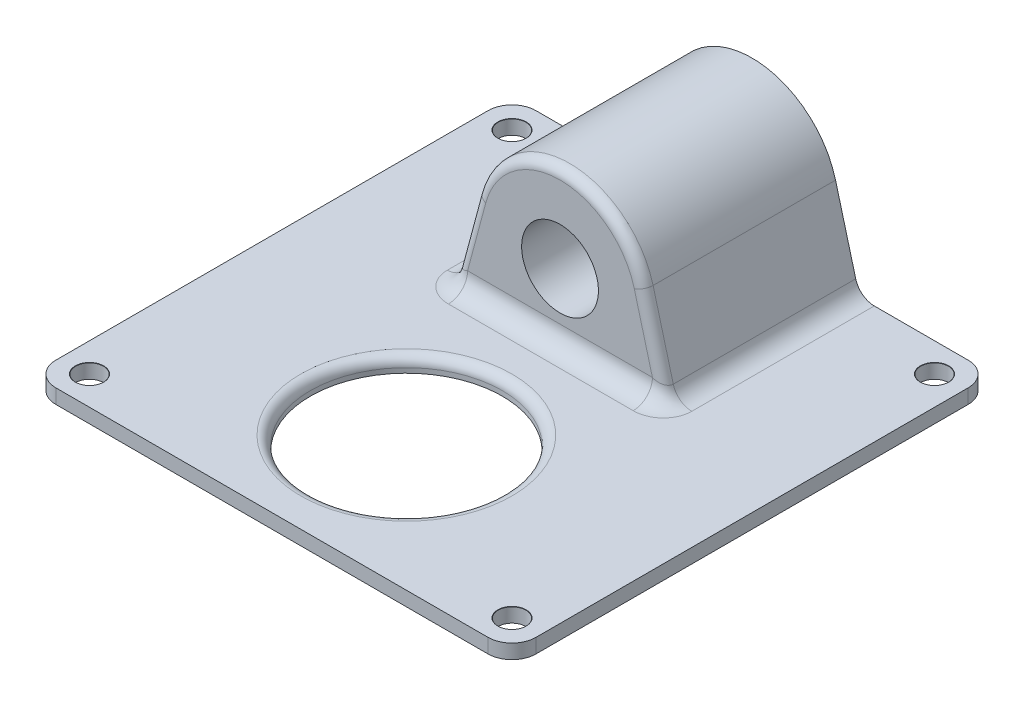
SolidWorks part; units mm, degrees
ref_plane "Front Plane" through (0, 0, 0) normal (0, 0, 1) x (1, 0, 0)
ref_plane "Top Plane" through (0, 0, 0) normal (0, 1, 0) x (1, 0, 0)
ref_plane "Right Plane" through (0, 0, 0) normal (1, 0, 0) x (0, 0, -1)
sketch "Sketch1" plane through (0, 0, 0) normal (0, 1, 0) x (1, 0, 0)
  line L5 (0, 0) -> (0, 25)
  line L6 (0, 25) -> (25, 25)
  line L7 (25, 25) -> (25, -25)
  line L8 (25, -25) -> (0, -25)
  line L9 (0, -25) -> (0, 0)
  dimension "D1" = 50
  dimension "D2" = 25
extrude "Boss-Extrude1" add sketch "Sketch1" along normal blind 1.5
sketch "Sketch2" plane through (0, 0, -25) normal (0, 0, -1) x (-1, 0, 0)
  line L0 (0, 4.5) -> (0, 1.5)
  line L1 (0, 1.5) -> (-11.1931, 1.5)
  line L2 (-25, 1.5) -> (0, 1.5) construction
  line L3 (-11.1931, 1.5) -> (-8.6933, 10.8294)
  line L4 (0, 17.5) -> (0, 12.5)
  line L5 (0, 0) -> (0, -1.5) construction
  arc A0 (0, 17.5) -> (-8.6933, 10.8294) centre (0, 8.5) ccw
  arc A1 (0, 12.5) -> (0, 4.5) centre (0, 8.5) ccw
  dimension "D1" = 4
  dimension "D2" = 5
  dimension "D3" = 15
  dimension "D4" = 1.5
  dimension "D5" = 10
extrude "Boss-Extrude2" add sketch "Sketch2" against normal blind 20
fillet "Fillet4" radius 1 2 edges at (9.9432, 6.1647, -5) (5.4789, 15.6402, -5)
fillet "Fillet1" radius 2 3 edges at (11.1931, 1.5, -15.5) (5.0789, 1.5, -5) (10.8899, 1.5, -5.2929)
fillet "Fillet2" radius 2.5 2 edges at (25, 0.75, 25) (25, 0.75, -25)
hole_wizard "M2.5 Clearance Hole1" positions "Sketch3" profile "Sketch4" hole size "M2.5" standard "ANSI Metric" end condition up to next
sketch "Sketch3" plane through (0, 1.5, 0) normal (0, 1, 0) x (1, 0, 0)
  line L0 (25, -22.5) -> (25, 22.5) construction
  line L1 (22.5, 25) -> (12.7278, 25) construction
  line L2 (0, -25) -> (22.5, -25) construction
  point P0 (22, 22)
  point P2 (22, -22)
  point P10 (0, 0)
  dimension "D1" = 3
  dimension "D2" = 3
  dimension "D3" = 3
sketch "Sketch4" plane through (22, 1.5, -22) normal (1, 0, 0) x (0, 0, 1)
  line L0 (0, 0) -> (0, 1.5)
  line L1 (0, 1.5) -> (1.45, 1.5)
  line L2 (1.45, 1.5) -> (1.45, 0.025)
  line L3 (1.45, 0.025) -> (1.475, 0)
  line L5 (1.475, 0) -> (0, 0)
  line L6 (-1.45, 0.025) -> (-1.475, 0) construction
  line L11 (0, -6.35) -> (0, 107.95) construction
  dimension "Thru Hole Dia." = 2.9
  dimension "Thru Hole Depth" = 1.5
  dimension "Near C'Sink Dia." = 2.95
  dimension "Near C'Sink Angle" = 90
sketch "Sketch5" plane through (0, 1.5, 0) normal (0, 1, 0) x (1, 0, 0)
  line L0 (0, 3) -> (0, -25) construction
  circle A0 centre (0, -11) radius 10
  dimension "D1" = 20
extrude "Cut-Extrude1" cut sketch "Sketch5" against normal through all
fillet "Fillet5" radius 1 1 edges at (10, 1.5, 11)
mirror "Mirror1" about plane through (0, 17.5, -5) normal (-1, 0, 0) of bodies 105 102
equation "\"D2@Sketch3\"=\"D1@Sketch3\""
equation "\"D3@Sketch3\"=\"D2@Sketch3\""
